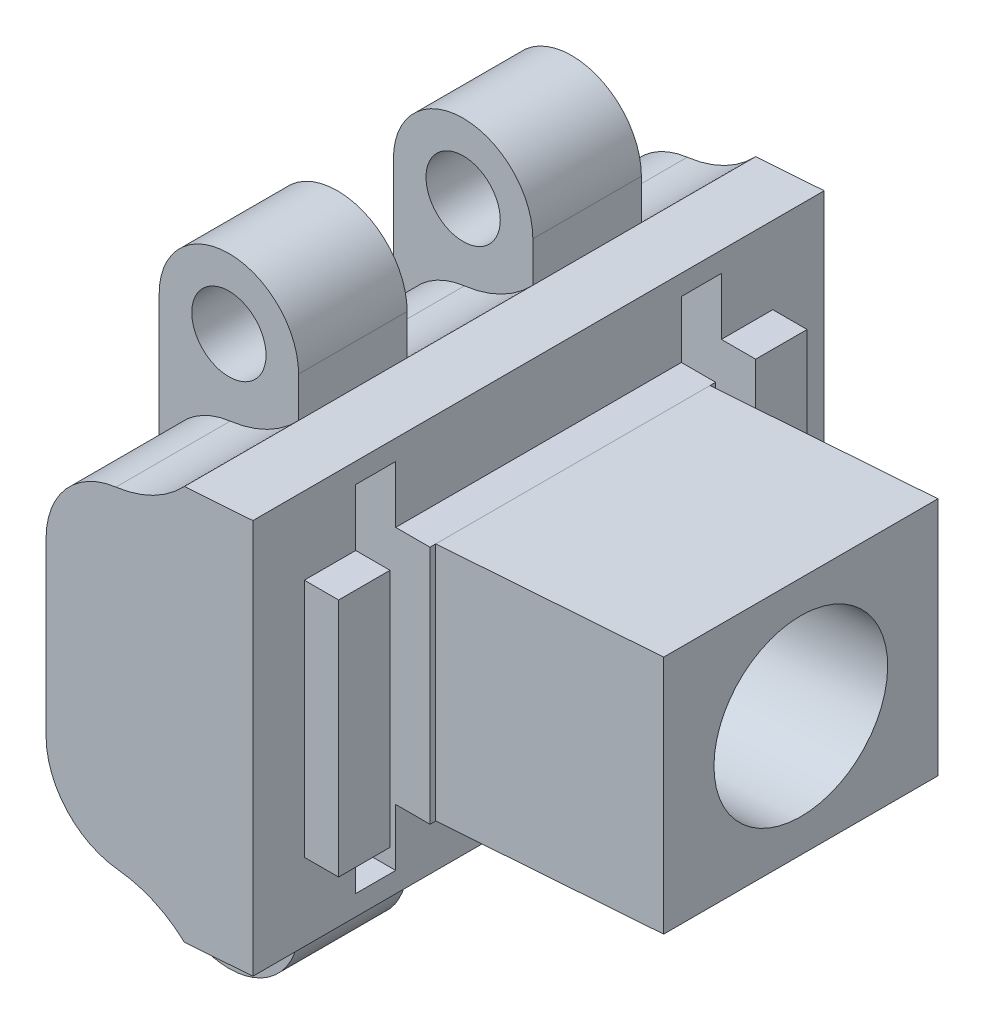
SolidWorks part; units mm, degrees
ref_plane "Front Plane" through (0, 0, 0) normal (0, 0, 1) x (1, 0, 0)
ref_plane "Top Plane" through (0, 0, 0) normal (0, 1, 0) x (1, 0, 0)
ref_plane "Right Plane" through (0, 0, 0) normal (1, 0, 0) x (0, 0, -1)
sketch "Sketch4" plane through (0, 0, 0) normal (0, 0, 1) x (1, 0, 0)
  line L0 (23.1832, 0) -> (-23.1832, 0) construction
  line L1 (7, -14.5) -> (-6, -14.5)
  line L2 (7, -14.5) -> (7, 14.5)
  line L3 (7, 14.5) -> (-6, 14.5)
  line L4 (-6, -14.5) -> (-6, 14.5)
  line L5 (7, -14.5) -> (-6, 14.5) construction
  line L6 (7, 14.5) -> (-6, -14.5) construction
  line L7 (0, -27.5) -> (0, 27.5) construction
  point P0 (0.5, 0)
  dimension "D1" = 6
  dimension "D2" = 7
  dimension "D3" = 29
extrude "Boss-Extrude1" add sketch "Sketch4" along normal blind 50
ref_plane "Plane1" through (0, 0, 14.75) normal (0, 0, 1) x (1, 0, 0)
ref_plane "Plane2" through (0, 0, 25) normal (0, 0, 1) x (1, 0, 0)
sketch "Sketch6" plane through (0, 0, 14.75) normal (0, 0, 1) x (1, 0, 0)
  line L0 (24.8332, 0) -> (-24.8332, 0) construction
  line L1 (0, -27.5) -> (0, 27.5) construction
  line L2 (-6.1, 21) -> (-6.1, 1)
  line L4 (-6.1, 1) -> (6.1, 1)
  line L5 (6.1, 1) -> (6.1, 21)
  circle A0 centre (0, 21) radius 3.25
  arc A1 (6.1, 21) -> (-6.1, 21) centre (0, 21) ccw
  arc A2 (-6.1, 21) -> (6.1, 21) centre (0, 21) ccw construction
  dimension "D1" = 6.5
  dimension "D2" = 12.2
  dimension "D3" = 21
  dimension "D4" = 20
extrude "Boss-Extrude2" add sketch "Sketch6" along normal blind 4.75 and the other way blind 4.75 contours L5 A1 L2 L4 A0 region at (0, 12.5003, 14.75)
mirror "Mirror1" about plane through (0, 0, 25) normal (0, 0, 1) of "Boss-Extrude2"
mirror "Mirror2" about plane through (0, 0, 0) normal (0, 1, 0) of "Mirror1", "Boss-Extrude2"
fillet "Fillet2" radius 7 6 edges at (-6, -14.5, 45) (-6, -14.5, 5) (-6, -14.5, 25) (-6, 14.5, 5) (-6, 14.5, 25) (-6, 14.5, 45)
ref_plane "Plane3" through (6.1, 0, 0) normal (1, 0, 0) x (0, 0, -1)
sketch "Sketch7" plane through (6.1, 0, 0) normal (1, 0, 0) x (0, 0, -1)
  line L0 (23.1832, 0) -> (-23.1832, 0) construction
  line L1 (0, -17.055) -> (-50, -17.055)
  line L2 (0, -17.055) -> (0, 17.055)
  line L3 (0, 17.055) -> (-50, 17.055)
  line L4 (-50, -17.055) -> (-50, 17.055)
  line L5 (0, -17.055) -> (-50, 17.055) construction
  line L6 (0, 17.055) -> (-50, -17.055) construction
  line L7 (-25, 7.15) -> (-25, -7.15) construction
  line L8 (-50, 14.5) -> (0, 14.5) construction
  point P0 (-25, 0)
  dimension "D1" = 34.11
extrude "Boss-Extrude3" add sketch "Sketch7" along normal blind 6
sketch "Sketch8" plane through (0, 0, 50) normal (0, 0, 1) x (1, 0, 0)
  line L0 (6.1, 17.4816) -> (12.1, 17.9011)
  line L1 (0, -27.5) -> (0, 27.5) construction
  line L2 (12.1, 17.9011) -> (12.1, 17.055)
  line L4 (6.1, 17.055) -> (18.7447, 17.055) construction
  line L5 (23.1832, 0) -> (-23.1832, 0) construction
  line L6 (6.1, 17.055) -> (12.1, 17.055)
  line L7 (6.1, 17.055) -> (6.1, 17.4816)
  line L8 (6.1, 14.5) -> (6.1, 17.055) construction
  line L10 (0, 17.055) -> (6.1, 17.4816) construction
  line L11 (0, 17.055) -> (6.1, 17.055) construction
  line L12 (0, 17.055) -> (6.1, 17.055) construction
  dimension "D1" = 4
  dimension "D2" = 17.055
extrude "Boss-Extrude4" add sketch "Sketch8" against normal up to surface (50 mm away) up to face at (3.5701, 0, 0)
sketch "Sketch9" plane through (0, 0, 50) normal (0, 0, 1) x (1, 0, 0)
  line L0 (6.1, -17.055) -> (17.7284, -16.2419)
  line L1 (6.1, -27.5) -> (6.1, 27.5) construction
  line L2 (17.7284, -16.2419) -> (17.7284, -20.1442)
  line L3 (17.7284, -20.1442) -> (6.1, -20.1442)
  line L4 (6.1, -20.1442) -> (6.1, -17.055)
  line L6 (23.1832, 0) -> (-23.1832, 0) construction
  dimension "D1" = 4
  dimension "D2" = 17.055
extrude "Cut-Extrude1" cut sketch "Sketch9" against normal through all
sketch "Sketch10" plane through (12.1, 0, 0) normal (1, 0, 0) x (0, 0, -1)
  line L0 (-25, 10.505) -> (-25, -10.505) construction
  line L1 (0, -16.6354) -> (-50, -16.6354) construction
  line L2 (0, -16.6354) -> (0, 17.9011) construction
  line L3 (0, 17.9011) -> (-50, 17.9011) construction
  line L4 (-50, -16.6354) -> (-50, 17.9011) construction
  line L5 (0, -16.6354) -> (-50, 17.9011) construction
  line L6 (0, 17.9011) -> (-50, -16.6354) construction
  line L7 (0, -16.6354) -> (-50, -16.6354) construction
  line L9 (-4.5, -9.8672) -> (-45.5, -9.8672)
  line L10 (-4.5, -9.8672) -> (-4.5, 11.1328)
  line L11 (-4.5, 11.1328) -> (-45.5, 11.1328)
  line L12 (-45.5, -9.8672) -> (-45.5, 11.1328)
  line L13 (-4.5, -9.8672) -> (-45.5, 11.1328) construction
  line L14 (-4.5, 11.1328) -> (-45.5, -9.8672) construction
  point P0 (-25, 0.6328)
  point P10 (-25, 0.6328)
  dimension "D1" = 41
  dimension "D2" = 21
extrude "Boss-Extrude5" add sketch "Sketch10" along normal blind 3 contours L10 L9 L12 L11
fillet "Fillet4" radius 10 6 edges at (6.1, -14.5, 45) (6.1, -14.5, 25) (6.1, -14.5, 5) (6.1, 14.5, 5) (6.1, 14.5, 25) (6.1, 14.5, 45)
sketch "Sketch11" plane through (12.1, 0, 0) normal (1, 0, 0) x (0, 0, -1)
  line L0 (-25, 9.955) -> (-25, -9.955) construction
  line L1 (0, -16.6354) -> (-50, -16.6354) construction
  line L2 (0, -16.6354) -> (0, 17.9011) construction
  line L3 (0, 17.9011) -> (-50, 17.9011) construction
  line L4 (-50, -16.6354) -> (-50, 17.9011) construction
  line L5 (0, -16.6354) -> (-50, 17.9011) construction
  line L6 (0, 17.9011) -> (-50, -16.6354) construction
  line L7 (0, -16.6354) -> (-50, -16.6354) construction
  line L8 (-9, 16.1328) -> (-12.5, 16.1328)
  line L9 (-41, -14.8672) -> (-37.5, -14.8672)
  line L10 (-41, -14.8672) -> (-41, 16.1328)
  line L11 (-41, 16.1328) -> (-37.5, 16.1328)
  line L12 (-37.5, -14.8672) -> (-37.5, 16.1328)
  line L13 (-41, -14.8672) -> (-37.5, 16.1328) construction
  line L14 (-41, 16.1328) -> (-37.5, -14.8672) construction
  line L15 (-12.5, -14.8672) -> (-12.5, 16.1328)
  line L16 (-9, -14.8672) -> (-12.5, -14.8672)
  line L17 (-9, -14.8672) -> (-9, 16.1328)
  point P0 (-25, 0.6328)
  point P10 (-39.25, 0.6328)
  dimension "D1" = 3.5
  dimension "D2" = 31
  dimension "D3" = 12.5
extrude "Cut-Extrude2" cut sketch "Sketch11" along normal through all and the other way blind 7
sketch "Sketch12" plane through (15.1, 0, 0) normal (1, 0, 0) x (0, 0, -1)
  line L0 (-25, 9.955) -> (-25, -9.955) construction
  line L1 (-12.5, -9.8672) -> (-37.5, -9.8672) construction
  line L2 (-12.5, -9.8672) -> (-12.5, 11.1328) construction
  line L3 (-12.5, 11.1328) -> (-37.5, 11.1328) construction
  line L4 (-37.5, -9.8672) -> (-37.5, 11.1328) construction
  line L5 (-12.5, -9.8672) -> (-37.5, 11.1328) construction
  line L6 (-12.5, 11.1328) -> (-37.5, -9.8672) construction
  line L7 (-12.5, -9.8672) -> (-37.5, -9.8672) construction
  line L9 (-13, -9.8672) -> (-37, -9.8672)
  line L10 (-13, -9.8672) -> (-13, 11.1328)
  line L11 (-13, 11.1328) -> (-37, 11.1328)
  line L12 (-37, -9.8672) -> (-37, 11.1328)
  line L13 (-13, -9.8672) -> (-37, 11.1328) construction
  line L14 (-13, 11.1328) -> (-37, -9.8672) construction
  point P0 (-25, 0.6328)
  point P10 (-25, 0.6328)
  dimension "D1" = 24
sketch "Sketch14" plane through (0, 0, 25) normal (0, 0, 1) x (1, 0, 0)
  line L0 (15.1, 11.1328) -> (34.3064, 12.4759) construction
  line L1 (15.1, -9.8672) -> (15.1, 11.1328) construction
  dimension "D1" = 94
extrude "Boss-Extrude7" add sketch "Sketch12" along direction (0.9976, 0.0698, 0) on the side of the normal blind 20
ref_plane "Plane4" through (35.7525, 2.5001, 0) normal (0.9976, 0.0698, 0) x (0, 0, -1)
sketch "Sketch15" plane through (35.7525, 2.5001, 0) normal (0.9976, 0.0698, 0) x (0, 0, -1)
  line L1 (-25, 9.955) -> (-25, -9.955) construction
  circle A0 centre (-25, -0.3964) radius 7.6
  dimension "D1" = 10.5
  dimension "D2" = 15.2
extrude "Cut-Extrude3" cut sketch "Sketch15" against normal blind 24
